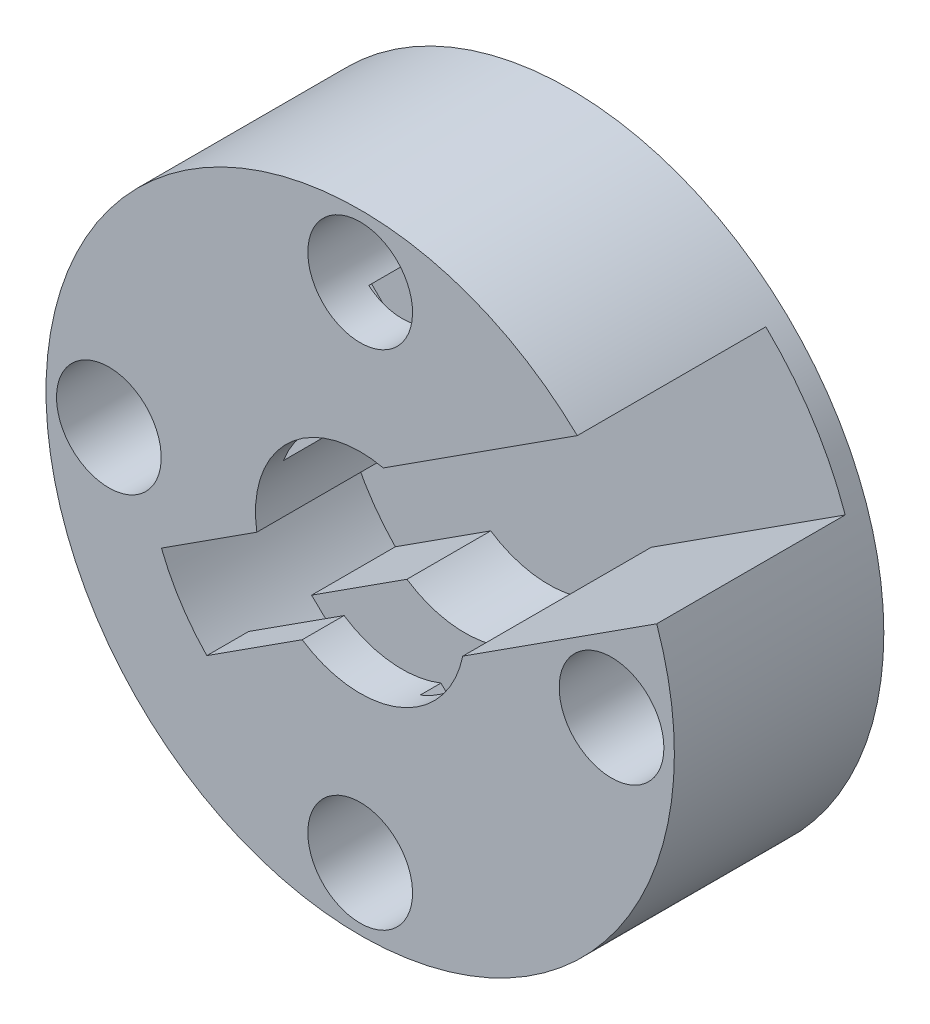
SolidWorks part; units mm, degrees
ref_plane "Front Plane" through (0, 0, 0) normal (0, 0, 1) x (1, 0, 0)
ref_plane "Top Plane" through (0, 0, 0) normal (0, 1, 0) x (1, 0, 0)
ref_plane "Right Plane" through (0, 0, 0) normal (1, 0, 0) x (0, 0, -1)
sketch "Sketch1" plane through (0, 0, 0) normal (0, 0, 1) x (1, 0, 0)
  circle A0 centre (0, 0) radius 15
  circle A1 centre (12, 0) radius 1.1
  circle A2 centre (12, 0) radius 2.5
  dimension "D1" = 30
  dimension "D2" = 2.2
  dimension "D3" = 12
  dimension "D4" = 5
extrude "Boss-Extrude1" add sketch "Sketch1" along normal blind 10 contours A2 A0 | A0 A2 A1 | A1 region at (-0.3429, 0, 0) region at (12, 0, 0) region at (9.5707, 0, 0)
extrude "screwthread cutout" cut sketch "Sketch1<3>" along normal through all contours A1 region at (12, 0, 0)
sketch "Sketch1<3>" plane through (0, 0, 0) normal (0, 0, 1) x (1, 0, 0) same geometry as "Sketch1"
extrude "screw head cutout" cut sketch "Sketch1<4>" along normal through all from offset 4 contours A0 A2 A1 | A1 region at (12, 0, 0) region at (9.5707, 0, 0)
sketch "Sketch1<4>" plane through (0, 0, 0) normal (0, 0, 1) x (1, 0, 0) same geometry as "Sketch1"
pattern_circular "CirPattern1" count 4 every 90 about axis through (0, 0, 10) along (0, 0, -1) of "screwthread cutout", "screw head cutout"
sketch "Sketch2" plane through (0, 0, 0) normal (0, 0, 1) x (1, 0, 0)
  line L0 (-9.4893, -3.7355) -> (7.3226, 7.0979)
  line L1 (-9.4893, -3.7355) -> (-7.3226, -7.0979)
  line L2 (7.3226, 7.0979) -> (9.4893, 3.7355)
  line L3 (-7.3226, -7.0979) -> (9.4893, 3.7355)
  line L4 (-9.4893, -3.7355) -> (9.4893, 3.7355) construction
  line L5 (7.3226, 7.0979) -> (-7.3226, -7.0979) construction
  line L6 (-4.2492, -9.2706) -> (4.2492, 9.2706)
  line L7 (-11.1334, -11.3379) -> (-14.925, -5.4538)
  line L8 (-11.1334, -11.3379) -> (14.925, 5.4538)
  line L9 (-14.925, -5.4538) -> (11.1334, 11.3379)
  line L10 (14.925, 5.4538) -> (11.1334, 11.3379)
  line L11 (-11.1334, -11.3379) -> (11.1334, 11.3379) construction
  line L12 (-14.925, -5.4538) -> (14.925, 5.4538) construction
  line L13 (5.7124, -8.448) -> (-8.5222, 5.6011)
  line L14 (5.7124, -8.448) -> (8.5222, -5.6011)
  line L15 (-8.5222, 5.6011) -> (-5.7124, 8.448)
  line L16 (8.5222, -5.6011) -> (-5.7124, 8.448)
  line L17 (5.7124, -8.448) -> (-5.7124, 8.448) construction
  line L18 (-8.5222, 5.6011) -> (8.5222, -5.6011) construction
  circle A0 centre (0, 0) radius 5
  circle A1 centre (0, 0) radius 7.5
  circle A2 centre (0, 0) radius 10.198
  point P14 (0, 0)
  dimension "D1" = 10
  dimension "D2" = 15
  dimension "D3" = 4
  dimension "D4" = 20
  dimension "D5" = 4.5
  dimension "D6" = 5
  dimension "D7" = 31
  dimension "D8" = 7
  dimension "D9" = 3
  dimension "D10" = 4
  dimension "D11" = 70
  dimension "D12" = 20
extrude "Cut-Extrude3" cut sketch "Sketch2" along normal through all from offset 1 contours A1 L3 L2 L0 | L3 A1 L0 A0 | L0 A1 L9 L6 A0 | L0 A2 L9 A1 | A0 L6 L9 | L8 A1 L3 A0 | L8 A2 L3 A1 | A2 L8 L10 L9 | L2 A2 | A1 L0 L1 L3 | L0 A1 L3 A0 | L1 A2 | A0 region at (-7.3164, -4.7146, 0) region at (-8.4726, -5.4596, 0) region at (-5.157, -3.3231, 0) region at (5.5534, 6.859, 0) region at (10.7125, 6.903, 0) region at (3.4161, 5.3745, 0) region at (5.157, 3.3231, 0) region at (1.9748, 5.1197, 0) region at (7.3164, 4.7146, 0) region at (8.4726, 5.4596, 0) region at (6.1587, 0.6755, 0) region at (8.5407, 2.223, 0)
extrude "Cut-Extrude4" cut sketch "Sketch2<4>" along normal blind 3 from offset 5 contours L6 A2 L16 A1 | L9 A2 L6 A1 | L0 A2 L9 A1 | L6 A1 L16 A0 L9 | L0 A1 L9 L6 A0 | L9 A1 L6 | L6 A0 L9 L16 L0 | L9 A0 L16 | L0 A0 L6 | L6 A0 L8 L13 L3 | L3 A0 L6 | L8 A0 L13 | L6 A1 L13 A0 L8 | A0 L6 L8 | L3 A1 L8 L6 A0 | L3 A2 L8 A1 | L8 A2 L6 A1 | L6 A2 L13 A1 | L8 A1 L6 | A0 L6 L9 | L0 L2 L3 L1 | L16 L15 L13 L14 region at (-5.5534, -6.859, 0) region at (-3.4161, -5.3745, 0) region at (-4.4882, -7.9018, 0) region at (-2.1379, -4.0337, 0) region at (-3.1731, -6.4229, 0) region at (0.5835, -8.5485, 0) region at (-0.5835, 8.5485, 0) region at (0.703, 3.7711, 0) region at (-0.703, -3.7711, 0) region at (-1.9748, -5.1197, 0) region at (-0.2491, 6.2069, 0) region at (0.2491, -6.2069, 0) region at (4.4882, 7.9018, 0) region at (2.1379, 4.0337, 0) region at (-0.4956, 4.484, 0) region at (0.4956, -4.484, 0) region at (3.1731, 6.4229, 0) region at (5.5534, 6.859, 0) region at (3.4161, 5.3745, 0) region at (1.9748, 5.1197, 0)
sketch "Sketch2<4>" plane through (0, 0, 0) normal (0, 0, 1) x (1, 0, 0) same geometry as "Sketch2"
extrude "Cut-Extrude11" cut sketch "Sketch2<5>" along normal blind 8 from offset 1 contours L16 L15 L13 L14
sketch "Sketch2<5>" plane through (0, 0, 0) normal (0, 0, 1) x (1, 0, 0) same geometry as "Sketch2"
